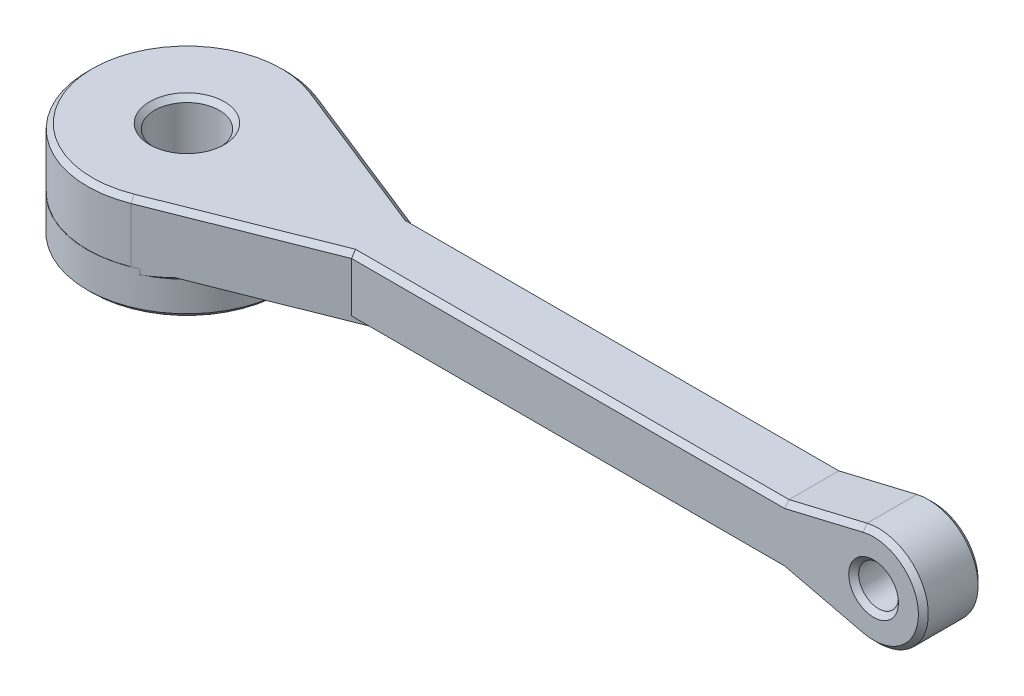
SolidWorks part; units mm, degrees
ref_plane "前视基准面" through (0, 0, 0) normal (0, 0, 1) x (1, 0, 0)
ref_plane "上视基准面" through (0, 0, 0) normal (0, 1, 0) x (1, 0, 0)
ref_plane "右视基准面" through (0, 0, 0) normal (1, 0, 0) x (0, 0, -1)
other "Configuration Table"
sketch "草图1" plane through (0, 0, 0) normal (0, 1, 0) x (1, 0, 0)
  line L0 (0, 0) -> (36, 0) construction
  line L1 (36, -1.5) -> (36, 1.5)
  line L2 (36, -1.5) -> (4.7697, -1.5)
  line L3 (36, 1.5) -> (4.7697, 1.5)
  arc A0 (4.7697, 1.5) -> (4.7697, -1.5) centre (0, 0) ccw
  point P7 (36, 0)
  dimension "D1" = 10
  dimension "D2" = 36
  dimension "D3" = 3
extrude "凸台-拉伸1" add sketch "草图1" along normal blind 3
sketch "草图2" plane through (0, 0, 0) normal (0, 0, 1) x (1, 0, 0)
  line L0 (36, 3) -> (36, 0) construction
  circle A0 centre (36, 1.5) radius 2.5
  dimension "D1" = 5
extrude "凸台-拉伸2" add sketch "草图2" against normal up to surface (1.5 mm away) from surface up to face at (20.3848, 1.5, -1.5) starting at face at (20.3848, 1.5, 1.5)
sketch "草图3" plane through (0, 0, 0) normal (0, 0, 1) x (1, 0, 0)
  circle A0 centre (36, 1.5) radius 1
  dimension "D1" = 2
extrude "切除-拉伸1" cut sketch "草图3" along normal up to surface (1.5 mm away) from surface up to face at (20.5098, 1.5, 1.5) starting at face at (20.5098, 1.5, -1.5)
sketch "草图5" plane through (0, 0, 0) normal (0, 0, 1) x (1, 0, 0)
  line L0 (31.5, 3) -> (35.4219, 3.9322)
  line L1 (31.5, 0) -> (35.4219, -0.9322)
  line L3 (4.7697, 0) -> (34, 0)
  line L4 (34, 3) -> (4.7697, 3)
  line L5 (4.7697, 3) -> (4.7697, 0)
  line L6 (31.5, 0) -> (34, 0)
  line L7 (34, 3) -> (31.5, 3)
  line L8 (4.7697, 3) -> (4.7697, 0)
  arc A0 (35.4219, 3.9322) -> (34, 3) centre (36, 1.5) ccw
  arc A1 (34, 0) -> (34, 3) centre (36, 1.5) ccw
  arc A2 (34, 0) -> (35.4219, -0.9322) centre (36, 1.5) ccw
  dimension "D2" = 2.5
  dimension "D3" = 2.5
  dimension "D1" = 0
extrude "凸台-拉伸3" add sketch "草图5" along normal up to surface (1.5 mm away) from surface contours A0 L0 L7 | A2 L6 L1 region at (33.4635, 3.2757, 0) region at (33.4635, -0.2757, 0) up to face at (35, 1.5, 1.5) starting at face at (37, 1.5, -1.5)
sketch "草图6" plane through (0, 0, 0) normal (0, 1, 0) x (1, 0, 0)
  line L0 (9.7697, 1.5) -> (1.8455, 4.647)
  line L1 (9.7697, -1.5) -> (1.8455, -4.647)
  line L3 (31.5, -1.5) -> (31.5, 1.5)
  line L4 (31.5, 1.5) -> (4.7697, 1.5)
  line L5 (4.7697, -1.5) -> (31.5, -1.5)
  line L6 (31.5, -1.5) -> (31.5, 1.5)
  line L7 (9.7697, 1.5) -> (4.7697, 1.5)
  line L8 (4.7697, -1.5) -> (9.7697, -1.5)
  arc A0 (1.8455, -4.647) -> (4.7697, -1.5) centre (0, 0) ccw
  arc A1 (4.7697, 1.5) -> (4.7697, -1.5) centre (0, 0) ccw
  arc A2 (4.7697, 1.5) -> (1.8455, 4.647) centre (0, 0) ccw
  dimension "D2" = 5
  dimension "D3" = 5
  dimension "D1" = 0
extrude "凸台-拉伸4" add sketch "草图6" along normal up to surface (3 mm away) contours A2 L7 L0 | A0 L1 L8 region at (5.898, 0, -2.4064) region at (5.898, 0, 2.4064) up to face at (15.6924, 3, 0)
sketch "草图7" plane through (0, 0, 0) normal (0, 1, 0) x (1, 0, 0)
  circle A0 centre (0, 0) radius 5.012
  dimension "D1" = 10.0241
extrude "凸台-拉伸5" add sketch "草图7" against normal blind 2
sketch "草图8" plane through (0, 0, 0) normal (0, 1, 0) x (1, 0, 0)
  line L1 (3.1754, 0) -> (1.5877, 2.75)
  line L2 (1.5877, 2.75) -> (-1.5877, 2.75)
  line L3 (-1.5877, 2.75) -> (-3.1754, 0)
  line L4 (-3.1754, 0) -> (-1.5877, -2.75)
  line L5 (-1.5877, -2.75) -> (1.5877, -2.75)
  line L6 (1.5877, -2.75) -> (3.1754, 0)
  circle A0 centre (0, 0) radius 2.75 construction
  dimension "D1" = 5.5
extrude "切除-拉伸2" cut sketch "草图8" along normal blind 2.5 from surface starting at face at (0, -2, 5.012)
sketch "草图9" plane through (0, 0, 0) normal (0, 1, 0) x (1, 0, 0)
  circle A0 centre (0, 0) radius 1.625
  dimension "D1" = 3.25
extrude "切除-拉伸3" cut sketch "草图9" against normal up to surface (2 mm away) from surface up to face at (0, -2, 5.012) starting at face at (13.2308, 3, 0)
chamfer "倒角3" distance 0.25 angle 45 18 edges at (0, -2, 5.012) (5.012, 0, 0) (0, 3, 1.625) (35, 1.5, 1.5) (37, 1.5, -1.5) (20.6348, 0, 1.5) (33.4609, -0.4661, 1.5) (38.5, 1.5, 1.5) (33.4609, 3.4661, 1.5) (20.6348, 3, 1.5) (5.8076, 3, 3.0735) (-5, 3, 0) (5.8076, 3, -3.0735) (20.6348, 3, -1.5) (20.6348, 0, -1.5) (33.4609, 3.4661, -1.5) (33.4609, -0.4661, -1.5) (38.5, 1.5, -1.5)
